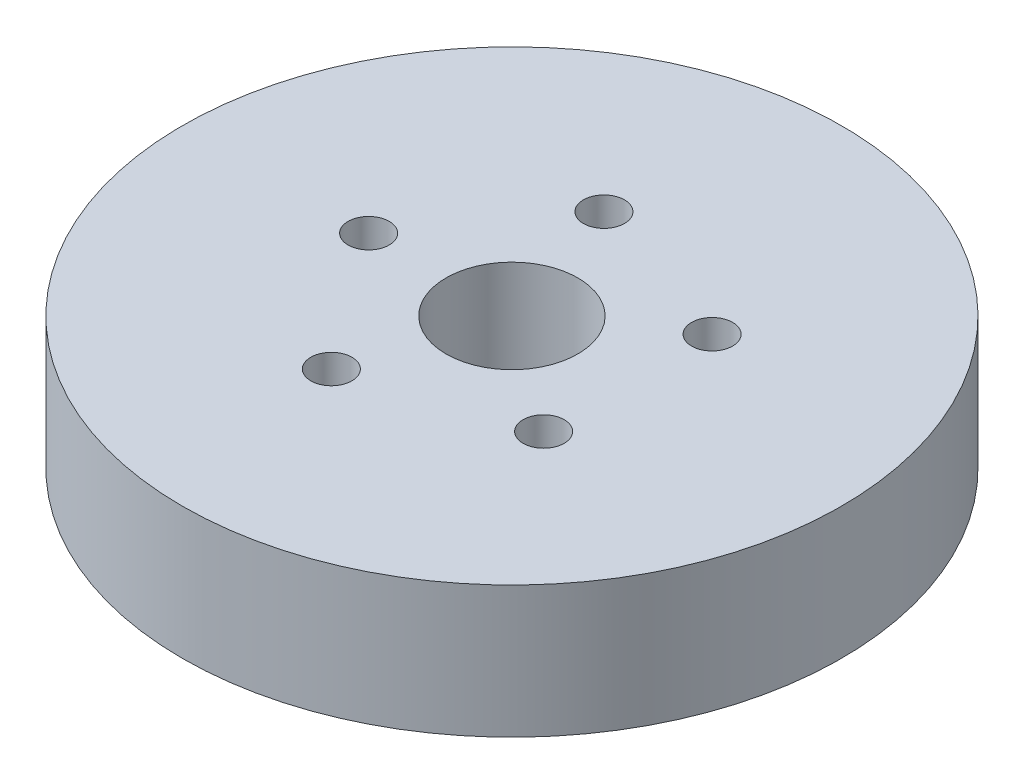
SolidWorks part; units mm, degrees
ref_plane "Front Plane" through (0, 0, 0) normal (0, 0, 1) x (1, 0, 0)
ref_plane "Top Plane" through (0, 0, 0) normal (0, 1, 0) x (1, 0, 0)
ref_plane "Right Plane" through (0, 0, 0) normal (1, 0, 0) x (0, 0, -1)
sketch "Sketch1" plane through (0, 0, 0) normal (0, 1, 0) x (1, 0, 0)
  circle A0 centre (0, 0) radius 50
  dimension "FLANGE_OD" = 100
extrude "Boss-Extrude1" add sketch "Sketch1" along normal blind 20
sketch "Sketch2" plane through (0, 0, 0) normal (0, 1, 0) x (1, 0, 0)
  circle A0 centre (0, 0) radius 10
  dimension "BORE_D" = 20
extrude "Cut-Extrude1" cut sketch "Sketch2" along normal through all
sketch "Sketch3" plane through (0, 20, 0) normal (0, 1, 0) x (1, 0, 0)
  circle A0 centre (0, 0) radius 21.7408 construction
  circle A1 centre (-21.7408, 0) radius 3.115
  dimension "BOLT_D" = 6.2299
  dimension "BOLT_PCD" = 43.4816
extrude "Cut-Extrude2" cut sketch "Sketch3" against normal blind 16.1579
pattern_circular "CirPattern1" count 5 over 360 about axis through (0, 0, 0) along (0, 1, 0) of "Cut-Extrude2"
